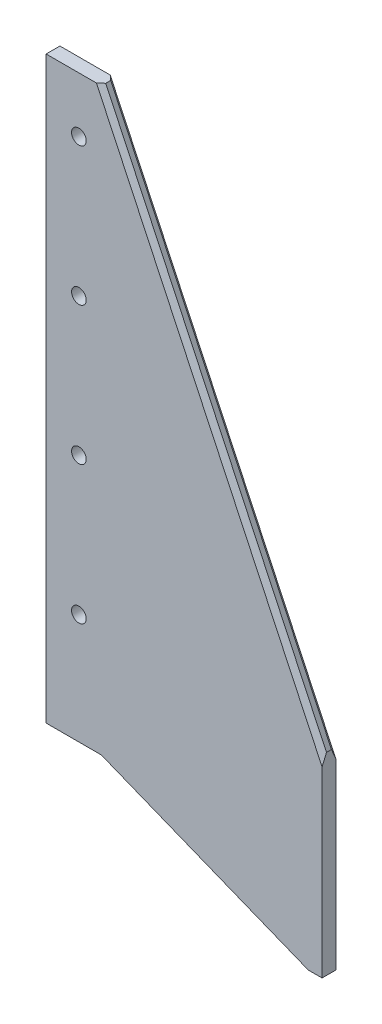
SolidWorks part; units mm, degrees
material "Pine"
ref_plane "Front Plane" through (0, 0, 0) normal (0, 0, 1) x (1, 0, 0)
ref_plane "Top Plane" through (0, 0, 0) normal (0, 1, 0) x (1, 0, 0)
ref_plane "Right Plane" through (0, 0, 0) normal (1, 0, 0) x (0, 0, -1)
sketch "Sketch1" plane through (0, 0, 0) normal (0, 0, 1) x (1, 0, 0)
  line L8 (0, 0) -> (0, 228.6) construction
  line L16 (101.6, 12.7) -> (101.6, -76.2)
  line L19 (0, 228.6) -> (101.6, 12.7)
  line L22 (0, 0) -> (-25.4, 0) construction
  line L24 (-25.4, 0) -> (0, 0) construction
  line L26 (-25.4, 0) -> (-25.4, -38.1)
  line L27 (-25.4, -38.1) -> (0, -38.1)
  line L30 (-25.4, 228.6) -> (-25.4, 0)
  line L31 (-25.4, 228.6) -> (0, 228.6)
  line L32 (101.6, -76.2) -> (95.25, -76.2)
  line L33 (95.25, -76.2) -> (0, -38.1)
  dimension "D1" = 25.4
  dimension "D2" = 304.8
  dimension "D3" = 127
  dimension "D4" = 76.2
  dimension "D5" = 88.9
  dimension "D6" = 38.1
  dimension "D7" = 6.35
  dimension "D9" = 25.4
extrude "Boss-Extrude1" add sketch "Sketch1" along normal blind 6.35 contours L16 L32 L33 L27 L26 L30 L31 L19
chamfer "Chamfer1" distance 2.032 angle 45 2 edges at (50.8, 120.65, 0) (50.8, 120.65, 6.35)
hole_wizard "1/4 Clearance Hole1" positions "Sketch2" profile "Sketch3" hole size "1/4" standard "ANSI Inch" end condition through all
sketch "Sketch2" plane through (0, 0, 6.35) normal (0, 0, 1) x (1, 0, 0)
  line L0 (-25.4, 228.6) -> (-25.4, -38.1) construction
  line L1 (-25.4, 228.6) -> (-2.2458, 228.6) construction
  point P0 (-10.3187, 203.2)
  dimension "D1" = 15.0812
  dimension "D2" = 25.4
sketch "Sketch3" plane through (-10.3187, 203.2, 6.35) normal (1, 0, 0) x (0, -1, 0)
  line L0 (0, 0) -> (0, 6.35)
  line L1 (0, 6.35) -> (3.3782, 6.35)
  line L2 (3.3782, 6.35) -> (3.3782, 0)
  line L5 (3.3782, 0) -> (0, 0)
  line L11 (0, -6.35) -> (0, 107.95) construction
  dimension "Thru Hole Dia." = 6.7564
  dimension "Thru Hole Depth" = 6.35
pattern_linear "LPattern1" count 4 spacing 63.5 along (0, -1, 0) of "1/4 Clearance Hole1"
